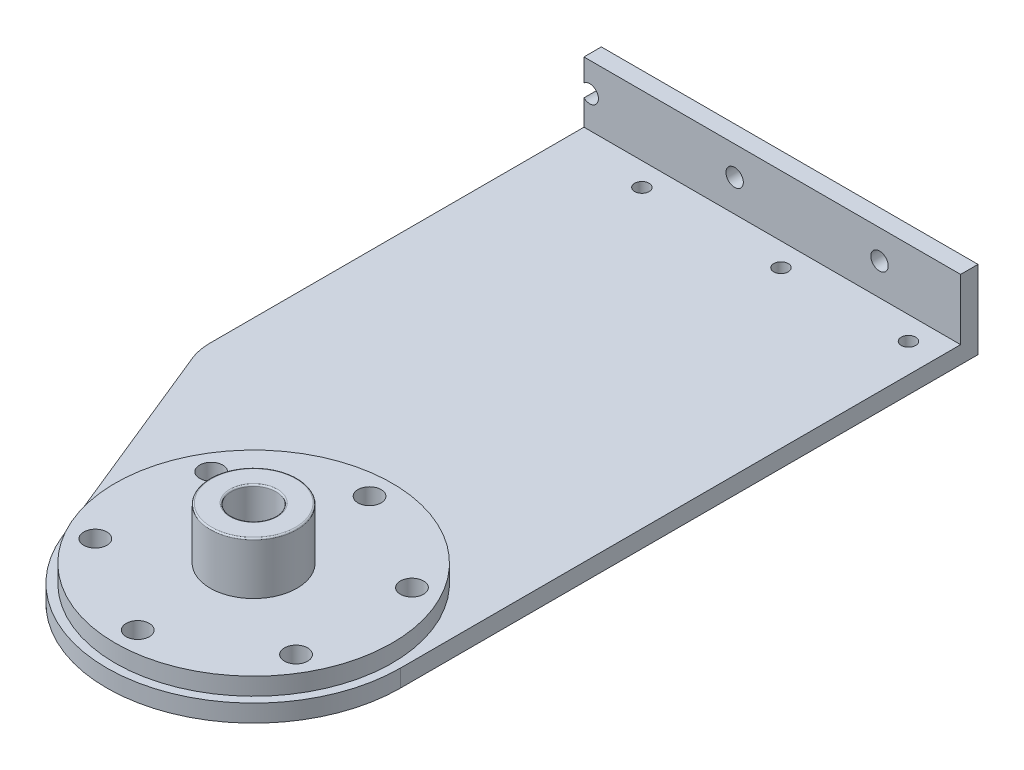
SolidWorks part; units mm, degrees
ref_plane "Plano frontal" through (0, 0, 0) normal (0, 0, 1) x (1, 0, 0)
ref_plane "Plano superior" through (0, 0, 0) normal (0, 1, 0) x (1, 0, 0)
ref_plane "Plano direito" through (0, 0, 0) normal (1, 0, 0) x (0, 0, -1)
sketch "Esboço1" plane through (0, 0, 0) normal (0, 1, 0) x (1, 0, 0)
  line L0 (-39.65, 96.65) -> (25.35, 96.65)
  line L2 (25.35, 0) -> (25.35, 96.65)
  line L4 (-39.65, 96.65) -> (-39.65, 32.1082)
  line L5 (-7.15, 96.65) -> (-7.15, 92.65) construction
  line L6 (-38.9114, 28.3365) -> (-23.4778, -9.5612)
  line L7 (-39.65, 92.65) -> (25.35, 92.65) construction
  circle A0 centre (0, 0) radius 23.9
  circle A1 centre (0, 0) radius 3.85
  circle A2 centre (0, 0) radius 7.5
  circle A3 centre (0, 0) radius 20 construction
  circle A4 centre (0, 20) radius 2
  circle A5 centre (17.3205, 10) radius 2
  circle A6 centre (17.3205, -10) radius 2
  circle A7 centre (0, -20) radius 2
  circle A8 centre (-17.3205, -10) radius 2
  circle A9 centre (-17.3205, 10) radius 2
  arc A10 (-23.4778, -9.5612) -> (25.35, 0) centre (0, 0) ccw
  circle A11 centre (0, 0) radius 25.35 construction
  arc A12 (-39.65, 32.1082) -> (-38.9114, 28.3365) centre (-29.65, 32.1082) ccw
  circle A13 centre (20.35, 92.65) radius 1.25
  circle A14 centre (-1.65, 92.65) radius 1.25
  circle A15 centre (-25.65, 92.65) radius 1.25
  point P21 (0, 0)
  point P28 (-39.65, 30.15)
  dimension "D1" = 47.8
  dimension "D2" = 7.7
  dimension "D3" = 15
  dimension "D4" = 40
  dimension "D5" = 4
  dimension "D10" = 96.65
  dimension "D11" = 10
  dimension "D13" = 2.5
  dimension "D8" = 65
  dimension "D9" = 66.5
  dimension "D12" = 4
  dimension "D14" = 5
  dimension "D15" = 22
  dimension "D16" = 24
  dimension "D7" = 1.45
  dimension "D6" = 6
extrude "Ressalto-extrusão1" add sketch "Esboço1" against normal blind 3 contours A0 A9 A8 A7 A6 A5 A4 A2 | L4 A12 L6 A10 L2 L0 A0 region at (-7.252, 0, -54.5811) region at (-23.224, 0, 0)
extrude "Ressalto-extrusão2" add sketch "Esboço1<3>" along normal blind 3 contours A4 | A5 | A6 | A7 | A8 | A9 | A1 | A0 | A8 | A9 region at (0, 0, 0) region at (0, 0, -20) region at (17.3205, 0, -10) region at (17.3205, 0, 10) region at (0, 0, 20) region at (-17.3205, 0, 10) region at (-17.3205, 0, -10)
sketch "Esboço1<3>" plane through (0, 0, 0) normal (0, 1, 0) x (1, 0, 0) same geometry as "Esboço1"
extrude "Ressalto-extrusão3" add sketch "Esboço1<4>" along normal blind 12 contours A2 A1 region at (-7.2879, 0, 0)
sketch "Esboço1<4>" plane through (0, 0, 0) normal (0, 1, 0) x (1, 0, 0) same geometry as "Esboço1"
fillet "Filete1" radius 0.25 2 edges at (0, 12, 3.85) (0, 12, 7.5)
sketch "Esboço2" plane through (0, 0, -96.65) normal (0, 0, -1) x (-1, 0, 0)
  line L0 (39.65, -3) -> (-25.35, -3) construction
  line L1 (39.65, -3) -> (-25.35, -3)
  line L2 (-25.35, -3) -> (-25.35, 10.5)
  line L3 (-25.35, 10.5) -> (39.65, 10.5)
  line L4 (39.65, 10.5) -> (39.65, -3)
  dimension "D1" = 13.5
extrude "Ressalto-extrusão4" add sketch "Esboço2" along normal blind 3
sketch "Esboço4" plane through (0, 0, -99.65) normal (0, 0, -1) x (-1, 0, 0)
  line L0 (-25.35, 10.5) -> (-25.35, -3) construction
  line L1 (39.65, 10.5) -> (-25.35, 10.5) construction
  circle A0 centre (-11.35, 5.5) radius 1.5
  circle A1 centre (13.65, 5.5) radius 1.5
  circle A2 centre (38.65, 5.5) radius 1.5
  point P10 (0, 0)
  point P11 (0, 0)
  dimension "D3" = 3
  dimension "D1" = 14
  dimension "D2" = 5
  dimension "D4" = 25
  dimension "D5" = 25
extrude "Corte-extrusão1" cut sketch "Esboço4" against normal up to surface (3 mm away) up to face at (-7.15, 5.25, -96.65)
